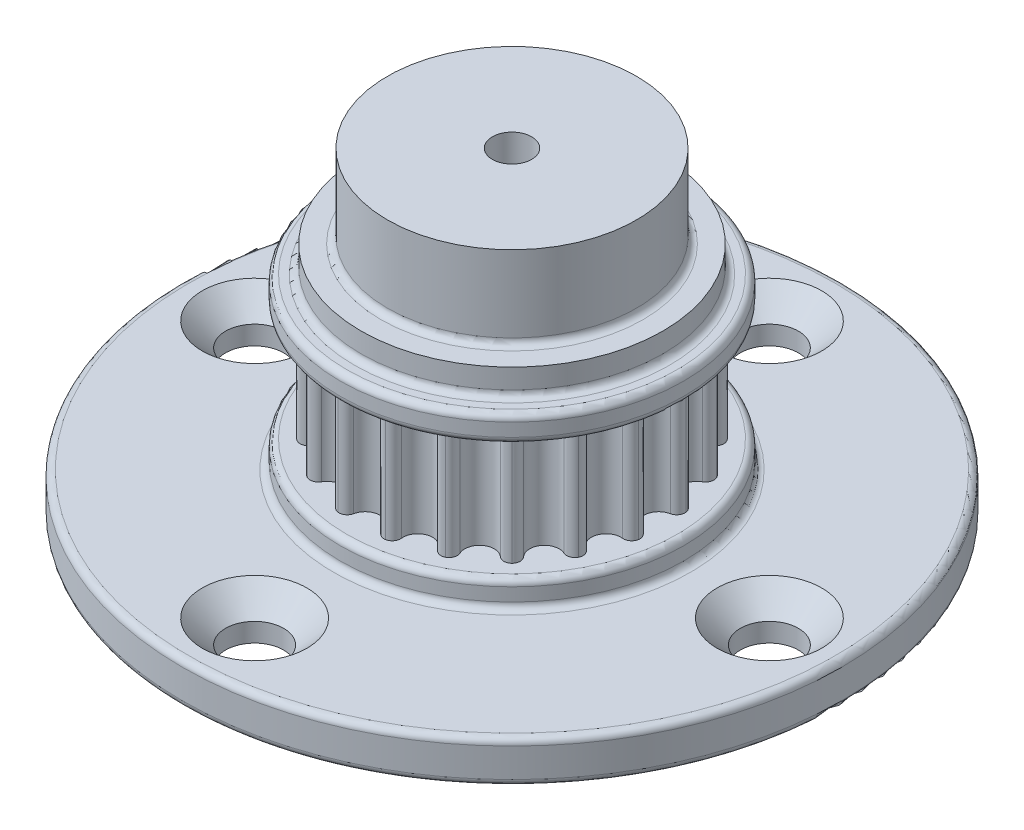
SolidWorks part; units mm, degrees
ref_plane "Front Plane" through (0, 0, 0) normal (0, 0, 1) x (1, 0, 0)
ref_plane "Top Plane" through (0, 0, 0) normal (0, 1, 0) x (1, 0, 0)
ref_plane "Right Plane" through (0, 0, 0) normal (1, 0, 0) x (0, 0, -1)
ref_plane "Plane1" through (0, 0, 0) normal (-0.7071, 0, 0.7071) x (0.7071, 0, 0.7071)
sketch "Sketch1" plane through (0, 0, 0) normal (0, 1, 0) x (1, 0, 0)
  line L0 (0, 0) -> (0, 9.1676) construction
  line L1 (0, 0) -> (2.731, 8.405) construction
  circle A0 centre (0, 0) radius 9.1676 construction
  circle A1 centre (0, 0) radius 7.9476 construction
  circle A2 centre (0, 8.8376) radius 0.89 construction
  circle A5 centre (2.731, 8.405) radius 0.89 construction
  arc A6 (0, 7.9476) -> (0.8721, 8.6598) centre (0, 8.8376) ccw
  arc A7 (0.8721, 8.6598) -> (1.4405, 9.0537) centre (1.362, 8.5599) cw
  arc A8 (1.4277, 9.0557) -> (1.8466, 8.5054) centre (1.3498, 8.5618) cw
  arc A9 (2.4559, 7.5586) -> (1.8466, 8.5054) centre (2.731, 8.405) cw
  arc A10 (1.4405, 9.0537) -> (1.4277, 9.0557) centre (0, 0) cw
  arc A11 (0, 7.9476) -> (2.4559, 7.5586) centre (0, 0) ccw
  dimension "D1" = 18.3352
  dimension "D3" = 1.78
  dimension "D4" = 0.5
  dimension "D2" = 1.22
  dimension "D5" = 18
extrude "Boss-Extrude1" add sketch "Sketch1" along normal mid plane 7.112 contours A6 A11 A9 A8 A7 region at (0.0089, 0, -0.0564)
ref_axis "Axis1" through (0, 3.3, 0) along (0, -1, 0)
pattern_circular "CirPattern1" count 20 over 360 about axis through (0, 3.3, 0) along (0, -1, 0) of "Boss-Extrude1"
sketch "Sketch2" plane through (0, 0, 0) normal (1, 0, 0) x (0, 0, -1)
  line L10 (0, 3.5) -> (10.3423, 3.5) construction
  line L11 (0, 3.5) -> (0, 5.0875) construction
  line L12 (0, 5.0875) -> (10.3423, 5.0875)
  line L15 (10.3423, 3.5) -> (10.3423, 5.0875) construction
  line L20 (0, 3.3) -> (0, -3.3) construction
  line L22 (10.3423, 5.0875) -> (0, 5.0875) construction
  line L23 (10.3423, 5.0875) -> (10.3423, 3.5)
  line L24 (10.3423, 3.5) -> (0, 3.5)
  line L25 (0, 5.0875) -> (0, 3.5)
  dimension "D1" = 1.5875
  dimension "D2" = 10.3423
  dimension "D3" = 3.5
revolve "Revolve3" add sketch "Sketch2" angle 360 about axis through (0, 3.3, 0) along (0, -1, 0) region at (0, 4.2937, -5.1712)
mirror "Mirror1" about plane through (0, 0, 0) normal (0, 1, 0) of "Revolve3"
sketch "Sketch9" plane through (0, -5.0875, 0) normal (0, -1, 0) x (1, 0, 0)
  circle A0 centre (0, 0) radius 19.8438
  circle A1 centre (0, 0) radius 1.5
  dimension "D1" = 3
  dimension "D2" = 39.6875
extrude "Boss-Extrude2" add sketch "Sketch9" along normal blind 2.54
sketch "Sketch3" plane through (0, 0, 0) normal (0, 1, 0) x (1, 0, 0)
  circle A0 centre (-15.5, 0) radius 1.7462
  circle A3 centre (0, 15.5) radius 1.7462
  circle A4 centre (15.5, 0) radius 1.7463
  circle A5 centre (0, -15.5) radius 1.7462
  dimension "D3" = 3.4925
  dimension "D1" = 15.5
  dimension "D4" = 4
extrude "Cut-Extrude1" cut sketch "Sketch3" against normal through all both and the other way through all
ref_axis "Axis2" through (-15.5, -7.6275, 0) along (0, 1, 0)
sketch "Sketch6" plane through (0, 0, 0) normal (0, 0, 1) x (1, 0, 0)
  line L0 (-19.1322, -3.5) -> (-11.8678, -3.5) construction
  line L1 (-5.7956, -3.5) -> (-6.4824, -3.5) construction
  line L2 (-11.8678, -3.5) -> (-15.5, -7.1322)
  line L3 (-15.5, -7.1322) -> (-19.1322, -3.5) construction
  line L4 (-18.548, -4.0842) -> (-12.452, -4.0842) construction
  line L5 (-17.2462, -3.998) -> (-13.7538, -3.998) construction
  line L8 (-15.5, -7.1322) -> (-15.5, -3.5)
  line L9 (-15.5, -3.5) -> (-11.8678, -3.5)
  line L10 (-15.5, -7.6275) -> (-15.5, -5.0875) construction
  line L12 (-17.2462, -5.0875) -> (-17.2462, -7.6275) construction
  line L13 (-13.7538, -7.6275) -> (-13.7538, -5.0875) construction
  point P2 (-15.5, -3.998)
  dimension "D1" = 6.096
  dimension "D2" = 0.5842
revolve "Cut-Revolve2" cut sketch "Sketch6" angle 360 about axis through (-15.5, -7.6275, 0) along (0, 1, 0)
hole_wizard "CSK for M3 Flat Head Machine Screw1" positions "3DSketch1" profile "Sketch13" countersink size "M3" standard "ANSI Metric"
sketch3d "3DSketch1"
  line L0 (-15.5, -5.0875, 0) -> (-15.5, -5.3859, 0) construction
  point P0 (-15.5, -5.0875, 0)
sketch "Sketch13" plane through (-15.5, -5.0875, 0) normal (1, 0, 0) x (0, 0, 1)
  line L0 (0, 0) -> (0, 25.9135)
  line L1 (0, 25.9135) -> (1.7, 24.892)
  line L2 (1.7, 24.892) -> (1.7, 1.45)
  line L3 (1.7, 1.45) -> (3.15, 0)
  line L5 (3.15, 0) -> (0, 0)
  line L6 (-1.7, 1.45) -> (-3.15, 0) construction
  line L10 (0, 25.9135) -> (-1.7, 24.892) construction
  line L11 (0, -6.35) -> (0, 107.95) construction
  dimension "Hole Dia." = 3.4
  dimension "Hole Depth" = 24.892
  dimension "Near C'Sink Dia." = 6.3
  dimension "Near C'Sink Angle" = 90
  dimension "Drill Angle" = 118
pattern_circular "CirPattern2" count 4 over 360 about axis through (0, 3.3, 0) along (0, -1, 0) of "Cut-Revolve2", "CSK for M3 Flat Head Machine Screw1"
sketch "Sketch11" plane through (0, -5.0875, 0) normal (0, -1, 0) x (1, 0, 0)
  circle A0 centre (0, 0) radius 1.5
  dimension "D1" = 3
extrude "Cut-Extrude2" cut sketch "Sketch11" against normal blind 6
sketch "Sketch10" plane through (0, 0, 0) normal (1, 0, 0) x (0, 0, -1)
  line L1 (1.1822, 6.675) -> (7.5, 6.675) construction
  line L2 (1.1822, 6.675) -> (1.1822, 11.675)
  line L3 (1.1822, 11.675) -> (7.5, 11.675)
  line L4 (7.5, 6.675) -> (7.5, 11.675)
  line L5 (0, 0) -> (0, 11.675) construction
  line L6 (10.3423, 5.0875) -> (-10.3423, 5.0875) construction
  line L7 (1.1822, 6.675) -> (9.0875, 6.675) construction
  line L8 (1.1822, 6.675) -> (1.1822, 5.0875)
  line L9 (1.1822, 5.0875) -> (9.0875, 5.0875)
  line L10 (9.0875, 6.675) -> (9.0875, 5.0875)
  line L11 (7.5, 6.675) -> (9.0875, 6.675)
  line L12 (0, 11.675) -> (1.1822, 11.675) construction
  dimension "D1" = 2.3644
  dimension "D2" = 5
  dimension "D3" = 1.5875
  dimension "D4" = 1.5875
  dimension "D5" = 15
revolve "Revolve4" add sketch "Sketch10" angle 360 about L5
fillet "Fillet1" radius 0.3969 8 edges at (0, 5.0875, 10.3423) (0, 3.5, 10.3423) (0, -7.6275, -19.8438) (0, -5.0875, -19.8438) (0, 6.675, -7.5) (0, 5.0875, -9.0875) (0, -3.5, 10.3423) (0, -5.0875, 10.3423)
equation "\"TEETH_NUM\"= 20"
equation "\"TOOTH_PITCH\"= 3mm"
equation "\"PITCH_LINE_OFFSET\"= .015in"
equation "\"DIAMETER_PER_GROOVE\"= \"OUTSIDE_DIAMETER\" / \"TEETH_NUM\" * 1in"
equation "\"PITCH_DIAMETER\"= ( ( \"TEETH_NUM\" * 3 - 1.31 ) / 3.1415 + .415 ) * 1mm"
equation "\"OUTSIDE_DIAMETER\"= \"PITCH_DIAMETER\" - \"PITCH_LINE_OFFSET\" * 2"
equation "\"D1@Sketch1\"=\"OUTSIDE_DIAMETER\""
equation "\"TOOTH_HEIGHT\"= 1.22mm"
equation "\"D2@Sketch1\"=\"TOOTH_HEIGHT\""
equation "\"TOOTH_DIAMETER\"= 1.78mm"
equation "\"INTERNAL_RADIUS\"= .5mm"
equation "\"D3@Sketch1\"=\"TOOTH_DIAMETER\""
equation "\"D5@Sketch1\"=360 / \"TEETH_NUM\""
equation "\"D4@Sketch1\"=\"INTERNAL_RADIUS\""
equation "\"D1@CirPattern1\"=\"TEETH_NUM\""
equation "\"BELT_GAP\"= 7mm"
equation "\"D2@Sketch2\"=\"PITCH_DIAMETER\"/2+1/32"
equation "\"D3@Sketch2\"=\"BELT_GAP\"/2"
